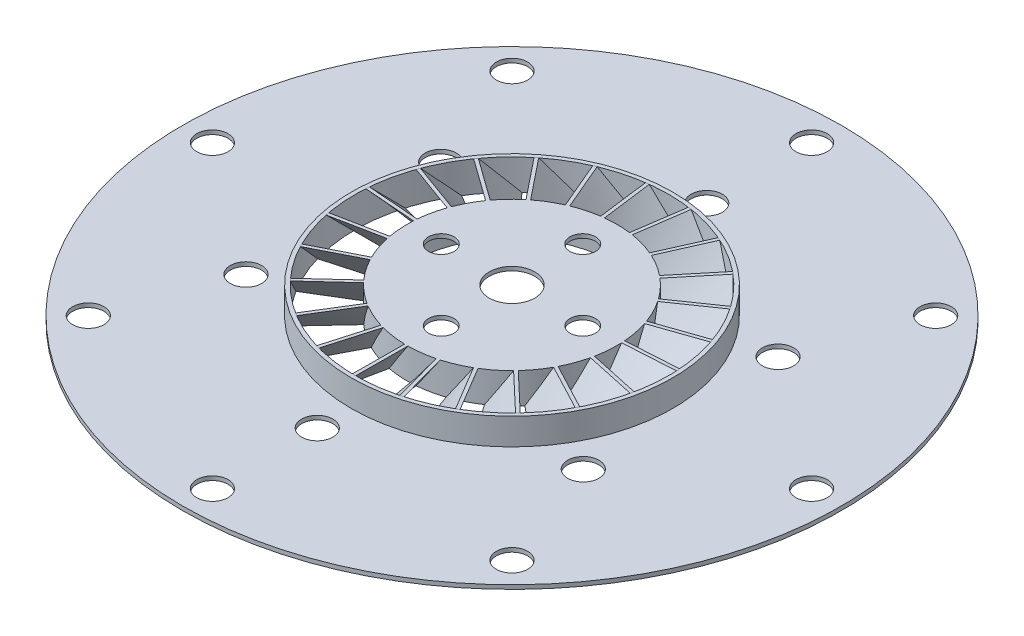
SolidWorks part; units mm, degrees
ref_plane "Front Plane" through (0, 0, 0) normal (0, 0, 1) x (1, 0, 0)
ref_plane "Top Plane" through (0, 0, 0) normal (0, 1, 0) x (1, 0, 0)
ref_plane "Right Plane" through (0, 0, 0) normal (1, 0, 0) x (0, 0, -1)
sketch "Sketch1" plane through (0, 0, 0) normal (0, 1, 0) x (1, 0, 0)
  circle A0 centre (0, 0) radius 33.25
  circle A1 centre (0, 0) radius 34.0882
  circle A2 centre (0, 0) radius 69.85
  circle A3 centre (0, 0) radius 22.25
  circle A4 centre (0, 0) radius 21.4118
  dimension "D1" = 66.5
  dimension "D2" = 0.8382
  dimension "D3" = 139.7
  dimension "D4" = 44.5
  dimension "D5" = 0.8382
extrude "Boss-Extrude1" add sketch "Sketch1" along normal blind 6.5 contours A1 A0 region at (-33.9918, 0, 0)
extrude "Boss-Extrude2" add sketch "Sketch1<3>" along normal blind 0.8636 contours A2 A1 region at (-67.8743, 0, 0)
sketch "Sketch1<3>" plane through (0, 0, 0) normal (0, 1, 0) x (1, 0, 0) same geometry as "Sketch1"
extrude "Boss-Extrude3" add sketch "Sketch1<4>" along normal blind 6.5 separate body contours A3 A4 region at (-21.6207, 0, 0)
sketch "Sketch1<4>" plane through (0, 0, 0) normal (0, 1, 0) x (1, 0, 0) same geometry as "Sketch1"
extrude "Boss-Extrude4" add sketch "Sketch1<5>" along normal blind 0.7 contours A4 region at (0, 0, 0)
sketch "Sketch1<5>" plane through (0, 0, 0) normal (0, 1, 0) x (1, 0, 0) same geometry as "Sketch1"
sketch "Sketch2" plane through (0, 0, 0) normal (0, -1, 0) x (1, 0, 0)
  line L0 (-31.9208, 9.3073) -> (-21.3278, 6.3393)
  line L1 (-33.2482, 0.35) -> (-22.2472, 0.35)
  line L2 (-33.2482, -0.35) -> (-22.2472, -0.35)
  line L3 (-32.1097, 8.6332) -> (-21.5167, 5.6652)
  line L4 (-28.226, 17.5743) -> (-18.8266, 11.8584)
  line L5 (-28.5897, 16.9762) -> (-19.1903, 11.2603)
  line L6 (-22.4378, 24.5378) -> (-14.9291, 16.498)
  line L7 (-22.9494, 24.0601) -> (-15.4407, 16.0202)
  line L8 (-14.9856, 29.6816) -> (-9.9244, 19.914)
  line L9 (-15.6071, 29.3595) -> (-10.5459, 19.592)
  line L10 (-6.4219, 32.624) -> (-4.1837, 21.8531)
  line L11 (-7.1072, 32.4815) -> (-4.869, 21.7107)
  line L12 (2.6181, 33.1468) -> (1.8674, 22.1715)
  line L13 (1.9198, 33.1945) -> (1.169, 22.2193)
  line L14 (11.4639, 31.2112) -> (7.7799, 20.8455)
  line L15 (10.8043, 31.4456) -> (7.1204, 21.0799)
  line L16 (19.4595, 26.9609) -> (13.1155, 17.9735)
  line L17 (18.8876, 27.3646) -> (12.5436, 18.3772)
  line L18 (26.0119, 20.711) -> (17.4783, 13.7685)
  line L19 (25.5701, 21.254) -> (17.0366, 14.3115)
  line L20 (30.635, 12.9251) -> (20.5449, 8.5423)
  line L21 (30.3561, 13.5671) -> (20.266, 9.1844)
  line L22 (32.9861, 4.1806) -> (22.0877, 2.6826)
  line L23 (32.8908, 4.874) -> (21.9924, 3.3761)
  line L24 (32.8908, -4.874) -> (21.9924, -3.3761)
  line L25 (32.9861, -4.1806) -> (22.0877, -2.6826)
  line L26 (30.3561, -13.5671) -> (20.266, -9.1844)
  line L27 (30.635, -12.9251) -> (20.5449, -8.5423)
  line L28 (25.5701, -21.254) -> (17.0366, -14.3115)
  line L29 (26.0119, -20.711) -> (17.4783, -13.7685)
  line L30 (18.8876, -27.3646) -> (12.5436, -18.3772)
  line L31 (19.4595, -26.9609) -> (13.1155, -17.9735)
  line L32 (10.8043, -31.4456) -> (7.1204, -21.0799)
  line L33 (11.4639, -31.2112) -> (7.7799, -20.8455)
  line L34 (1.9198, -33.1945) -> (1.169, -22.2193)
  line L35 (2.6181, -33.1468) -> (1.8674, -22.1715)
  line L36 (-7.1072, -32.4815) -> (-4.869, -21.7107)
  line L37 (-6.4219, -32.624) -> (-4.1837, -21.8531)
  line L38 (-15.6071, -29.3595) -> (-10.5459, -19.592)
  line L39 (-14.9856, -29.6816) -> (-9.9244, -19.914)
  line L40 (-22.9494, -24.0601) -> (-15.4407, -16.0202)
  line L41 (-22.4378, -24.5378) -> (-14.9291, -16.498)
  line L42 (-28.5897, -16.9762) -> (-19.1903, -11.2603)
  line L43 (-28.226, -17.5743) -> (-18.8266, -11.8584)
  line L44 (-32.1097, -8.6332) -> (-21.5167, -5.6652)
  line L45 (-31.9208, -9.3073) -> (-21.3278, -6.3393)
  circle A0 centre (0, 0) radius 33.25 construction
  circle A1 centre (0, 0) radius 22.25
  arc A2 (-21.3278, 6.3393) -> (-21.5167, 5.6652) centre (0, 0) ccw
  arc A3 (-18.8266, 11.8584) -> (-19.1903, 11.2603) centre (0, 0) ccw
  circle A5 centre (0, 0) radius 22.25 construction
  arc A6 (-31.9208, 9.3073) -> (-32.1097, 8.6332) centre (0, 0) ccw
  arc A7 (-28.226, 17.5743) -> (-28.5897, 16.9762) centre (0, 0) ccw
  arc A8 (-22.4378, 24.5378) -> (-22.9494, 24.0601) centre (0, 0) ccw
  arc A9 (-14.9291, 16.498) -> (-15.4407, 16.0202) centre (0, 0) ccw
  arc A10 (-9.9244, 19.914) -> (-10.5459, 19.592) centre (0, 0) ccw
  arc A11 (-14.9856, 29.6816) -> (-15.6071, 29.3595) centre (0, 0) ccw
  arc A12 (-6.4219, 32.624) -> (-7.1072, 32.4815) centre (0, 0) ccw
  arc A13 (-4.1837, 21.8531) -> (-4.869, 21.7107) centre (0, 0) ccw
  arc A14 (1.8674, 22.1715) -> (1.169, 22.2193) centre (0, 0) ccw
  arc A15 (2.6181, 33.1468) -> (1.9198, 33.1945) centre (0, 0) ccw
  arc A16 (11.4639, 31.2112) -> (10.8043, 31.4456) centre (0, 0) ccw
  arc A17 (7.7799, 20.8455) -> (7.1204, 21.0799) centre (0, 0) ccw
  arc A18 (13.1155, 17.9735) -> (12.5436, 18.3772) centre (0, 0) ccw
  arc A19 (19.4595, 26.9609) -> (18.8876, 27.3646) centre (0, 0) ccw
  arc A20 (26.0119, 20.711) -> (25.5701, 21.254) centre (0, 0) ccw
  arc A21 (17.4783, 13.7685) -> (17.0366, 14.3115) centre (0, 0) ccw
  arc A22 (20.5449, 8.5423) -> (20.266, 9.1844) centre (0, 0) ccw
  arc A23 (30.635, 12.9251) -> (30.3561, 13.5671) centre (0, 0) ccw
  arc A24 (32.9861, 4.1806) -> (32.8908, 4.874) centre (0, 0) ccw
  arc A25 (22.0877, 2.6826) -> (21.9924, 3.3761) centre (0, 0) ccw
  arc A26 (21.9924, -3.3761) -> (22.0877, -2.6826) centre (0, 0) ccw
  arc A27 (32.8908, -4.874) -> (32.9861, -4.1806) centre (0, 0) ccw
  arc A28 (-22.2472, 0.35) -> (-22.2472, -0.35) centre (0, 0) ccw
  arc A29 (-33.2482, 0.35) -> (-33.2482, -0.35) centre (0, 0) ccw
  arc A30 (-21.5167, -5.6652) -> (-21.3278, -6.3393) centre (0, 0) ccw
  arc A31 (-32.1097, -8.6332) -> (-31.9208, -9.3073) centre (0, 0) ccw
  arc A32 (-19.1903, -11.2603) -> (-18.8266, -11.8584) centre (0, 0) ccw
  arc A33 (-28.5897, -16.9762) -> (-28.226, -17.5743) centre (0, 0) ccw
  arc A34 (-22.9494, -24.0601) -> (-22.4378, -24.5378) centre (0, 0) ccw
  arc A35 (-15.4407, -16.0202) -> (-14.9291, -16.498) centre (0, 0) ccw
  arc A36 (-10.5459, -19.592) -> (-9.9244, -19.914) centre (0, 0) ccw
  arc A37 (-15.6071, -29.3595) -> (-14.9856, -29.6816) centre (0, 0) ccw
  arc A38 (-7.1072, -32.4815) -> (-6.4219, -32.624) centre (0, 0) ccw
  arc A39 (-4.869, -21.7107) -> (-4.1837, -21.8531) centre (0, 0) ccw
  arc A40 (1.169, -22.2193) -> (1.8674, -22.1715) centre (0, 0) ccw
  arc A41 (1.9198, -33.1945) -> (2.6181, -33.1468) centre (0, 0) ccw
  arc A42 (10.8043, -31.4456) -> (11.4639, -31.2112) centre (0, 0) ccw
  arc A43 (7.1204, -21.0799) -> (7.7799, -20.8455) centre (0, 0) ccw
  arc A44 (12.5436, -18.3772) -> (13.1155, -17.9735) centre (0, 0) ccw
  arc A45 (18.8876, -27.3646) -> (19.4595, -26.9609) centre (0, 0) ccw
  arc A46 (25.5701, -21.254) -> (26.0119, -20.711) centre (0, 0) ccw
  arc A47 (17.0366, -14.3115) -> (17.4783, -13.7685) centre (0, 0) ccw
  arc A48 (20.266, -9.1844) -> (20.5449, -8.5423) centre (0, 0) ccw
  arc A49 (30.3561, -13.5671) -> (30.635, -12.9251) centre (0, 0) ccw
  point P106 (0, 0)
  dimension "D3" = 0.7
  dimension "D1" = 0
  dimension "D4" = 23
sketch "Sketch3" plane through (0, 6.5, 0) normal (0, 1, 0) x (1, 0, 0)
  line L0 (0, 0) -> (-32.6054, -6.5152) construction
  line L1 (0, 0) -> (-15.6581, 0) construction
  line L2 (-21.8846, -4.016) -> (-32.6722, -6.1716)
  line L3 (-21.7474, -4.7025) -> (-32.535, -6.8581)
  line L4 (-22.1565, 2.0373) -> (-33.1257, 2.8721)
  line L5 (-22.2097, 1.3393) -> (-33.1788, 2.1741)
  line L6 (-20.7853, 7.9395) -> (-31.1225, 11.7028)
  line L7 (-21.0247, 7.2817) -> (-31.3619, 11.045)
  line L8 (-17.8724, 13.2529) -> (-26.811, 19.6656)
  line L9 (-18.2805, 12.6841) -> (-27.219, 19.0968)
  line L10 (-13.6341, 17.5833) -> (-20.511, 26.1698)
  line L11 (-14.1805, 17.1457) -> (-21.0574, 25.7322)
  line L12 (-8.3846, 20.6097) -> (-12.6899, 30.7332)
  line L13 (-9.0288, 20.3358) -> (-13.3341, 30.4592)
  line L14 (-2.5132, 22.1076) -> (-3.9276, 33.0172)
  line L15 (-3.2074, 22.0176) -> (-4.6218, 32.9272)
  line L16 (3.5445, 21.9659) -> (5.126, 32.8525)
  line L17 (2.8518, 22.0665) -> (4.4332, 32.9531)
  line L18 (9.3394, 20.195) -> (13.7994, 30.2513)
  line L19 (8.6995, 20.4788) -> (13.1595, 30.5351)
  line L20 (14.4416, 16.9264) -> (21.4494, 25.4064)
  line L21 (13.902, 17.3723) -> (20.9098, 25.8524)
  line L22 (18.4728, 12.4024) -> (27.5085, 18.6773)
  line L23 (18.0735, 12.9774) -> (27.1093, 19.2523)
  line L24 (21.1339, 6.9586) -> (31.5275, 10.563)
  line L25 (20.9045, 7.6199) -> (31.2982, 11.2244)
  line L26 (22.2276, 0.9987) -> (33.2083, 1.6653)
  line L27 (22.1852, 1.6974) -> (33.1659, 2.364)
  line L28 (21.6728, -5.0353) -> (32.4261, -7.356)
  line L29 (21.8204, -4.351) -> (32.5738, -6.6717)
  line L30 (19.5106, -10.6958) -> (29.239, -15.8316)
  line L31 (19.8374, -10.0768) -> (29.5658, -15.2126)
  line L32 (15.9014, -15.563) -> (23.8835, -23.1332)
  line L33 (16.3831, -15.0551) -> (24.3652, -22.6252)
  line L34 (11.1129, -19.2761) -> (16.7565, -28.719)
  line L35 (11.7137, -18.917) -> (17.3574, -28.3599)
  line L36 (5.5001, -21.5595) -> (8.3869, -32.1749)
  line L37 (6.1756, -21.3758) -> (9.0623, -31.9912)
  line L38 (-0.5205, -22.2439) -> (-0.6048, -33.2445)
  line L39 (0.1795, -22.2493) -> (0.0952, -33.2499)
  line L40 (-6.5025, -21.2786) -> (-9.5516, -31.8485)
  line L41 (-5.83, -21.4726) -> (-8.8791, -32.0425)
  line L42 (-12.0023, -18.7352) -> (-17.7901, -28.0905)
  line L43 (-11.407, -19.1035) -> (-17.1948, -28.4588)
  line L44 (-16.6119, -14.8023) -> (-24.7091, -22.2491)
  line L45 (-16.1381, -15.3175) -> (-24.2352, -22.7644)
  line L46 (-19.9895, -9.7715) -> (-29.7956, -14.7576)
  line L47 (-19.6722, -10.3955) -> (-29.4783, -15.3816)
  circle A0 centre (0, 0) radius 33.25 construction
  circle A1 centre (0, 0) radius 22.25 construction
  arc A2 (-32.6722, -6.1716) -> (-32.535, -6.8581) centre (0, 0) ccw
  arc A3 (-21.8846, -4.016) -> (-21.7474, -4.7025) centre (0, 0) ccw
  arc A4 (-22.1565, 2.0373) -> (-22.2097, 1.3393) centre (0, 0) ccw
  arc A5 (-33.1257, 2.8721) -> (-33.1788, 2.1741) centre (0, 0) ccw
  arc A6 (-20.7853, 7.9395) -> (-21.0247, 7.2817) centre (0, 0) ccw
  arc A7 (-31.1225, 11.7028) -> (-31.3619, 11.045) centre (0, 0) ccw
  arc A8 (-17.8724, 13.2529) -> (-18.2805, 12.6841) centre (0, 0) ccw
  arc A9 (-26.811, 19.6656) -> (-27.219, 19.0968) centre (0, 0) ccw
  arc A10 (-13.6341, 17.5833) -> (-14.1805, 17.1457) centre (0, 0) ccw
  arc A11 (-20.511, 26.1698) -> (-21.0574, 25.7322) centre (0, 0) ccw
  arc A12 (-8.3846, 20.6097) -> (-9.0288, 20.3358) centre (0, 0) ccw
  arc A13 (-12.6899, 30.7332) -> (-13.3341, 30.4592) centre (0, 0) ccw
  arc A14 (-2.5132, 22.1076) -> (-3.2074, 22.0176) centre (0, 0) ccw
  arc A15 (-3.9276, 33.0172) -> (-4.6218, 32.9272) centre (0, 0) ccw
  arc A16 (3.5445, 21.9659) -> (2.8518, 22.0665) centre (0, 0) ccw
  arc A17 (5.126, 32.8525) -> (4.4332, 32.9531) centre (0, 0) ccw
  arc A18 (9.3394, 20.195) -> (8.6995, 20.4788) centre (0, 0) ccw
  arc A19 (13.7994, 30.2513) -> (13.1595, 30.5351) centre (0, 0) ccw
  arc A20 (14.4416, 16.9264) -> (13.902, 17.3723) centre (0, 0) ccw
  arc A21 (21.4494, 25.4064) -> (20.9098, 25.8524) centre (0, 0) ccw
  arc A22 (18.4728, 12.4024) -> (18.0735, 12.9774) centre (0, 0) ccw
  arc A23 (27.5085, 18.6773) -> (27.1093, 19.2523) centre (0, 0) ccw
  arc A24 (21.1339, 6.9586) -> (20.9045, 7.6199) centre (0, 0) ccw
  arc A25 (31.5275, 10.563) -> (31.2982, 11.2244) centre (0, 0) ccw
  arc A26 (22.2276, 0.9987) -> (22.1852, 1.6974) centre (0, 0) ccw
  arc A27 (33.2083, 1.6653) -> (33.1659, 2.364) centre (0, 0) ccw
  arc A28 (21.6728, -5.0353) -> (21.8204, -4.351) centre (0, 0) ccw
  arc A29 (32.4261, -7.356) -> (32.5738, -6.6717) centre (0, 0) ccw
  arc A30 (19.5106, -10.6958) -> (19.8374, -10.0768) centre (0, 0) ccw
  arc A31 (29.239, -15.8316) -> (29.5658, -15.2126) centre (0, 0) ccw
  arc A32 (15.9014, -15.563) -> (16.3831, -15.0551) centre (0, 0) ccw
  arc A33 (23.8835, -23.1332) -> (24.3652, -22.6252) centre (0, 0) ccw
  arc A34 (11.1129, -19.2761) -> (11.7137, -18.917) centre (0, 0) ccw
  arc A35 (16.7565, -28.719) -> (17.3574, -28.3599) centre (0, 0) ccw
  arc A36 (5.5001, -21.5595) -> (6.1756, -21.3758) centre (0, 0) ccw
  arc A37 (8.3869, -32.1749) -> (9.0623, -31.9912) centre (0, 0) ccw
  arc A38 (-0.5205, -22.2439) -> (0.1795, -22.2493) centre (0, 0) ccw
  arc A39 (-0.6048, -33.2445) -> (0.0952, -33.2499) centre (0, 0) ccw
  arc A40 (-6.5025, -21.2786) -> (-5.83, -21.4726) centre (0, 0) ccw
  arc A41 (-9.5516, -31.8485) -> (-8.8791, -32.0425) centre (0, 0) ccw
  arc A42 (-12.0023, -18.7352) -> (-11.407, -19.1035) centre (0, 0) ccw
  arc A43 (-17.7901, -28.0905) -> (-17.1948, -28.4588) centre (0, 0) ccw
  arc A44 (-16.6119, -14.8023) -> (-16.1381, -15.3175) centre (0, 0) ccw
  arc A45 (-24.7091, -22.2491) -> (-24.2352, -22.7644) centre (0, 0) ccw
  arc A46 (-19.9895, -9.7715) -> (-19.6722, -10.3955) centre (0, 0) ccw
  arc A47 (-29.7956, -14.7576) -> (-29.4783, -15.3816) centre (0, 0) ccw
  point P101 (0, 0)
  dimension "D1" = 11.3
  dimension "D2" = 0.35
  dimension "D3" = 0.35
  dimension "D4" = 23
loft "Loft1" add section "Sketch2" section "Sketch3" connector at (-32.1097, 0, 8.6332) connector at (-29.7956, 6.5, 14.7576)
pattern_circular "CirPattern1" count 23 over 360 about axis through (0, 6.5, 0) along (0, -1, 0) of "Loft1"
sketch "Sketch4" plane through (0, 6.5, 0) normal (0, 1, 0) x (1, 0, 0)
  circle A0 centre (0, 0) radius 21.55
  dimension "D1" = 43.1
extrude "Boss-Extrude5" add sketch "Sketch4" against normal blind 0.8382
sketch "Sketch6" plane through (0, 0, 0) normal (0, -1, 0) x (1, 0, 0)
  line L0 (0, 0) -> (0, 14.9949) construction
  line L1 (0, 0) -> (14.9949, 0) construction
  line L2 (0, 0) -> (0, -14.9949) construction
  line L3 (0, 0) -> (-14.9949, 0) construction
  point P9 (0, 0)
  dimension "D1" = 14.9949
  dimension "D2" = 4
hole_wizard "CBORE for M5 Hex Head Bolt1" positions "3DSketch4" profile "Sketch7" counterbore size "M5" standard "ANSI Metric" end condition through all
sketch3d "3DSketch4"
  point P0 (0, 0, 14.9949)
  point P3 (14.9949, 0, 0)
  point P6 (0, 0, -14.9949)
  point P9 (-14.9949, 0, 0)
sketch "Sketch7" plane through (0, 0, 14.9949) normal (1, 0, 0) x (0, 0, -1)
  line L0 (0, 0) -> (0, 6.5001)
  line L1 (0, 6.5001) -> (2.7, 6.5001)
  line L3 (2.7, 6.5001) -> (2.7, 3.58)
  line L4 (2.7, 3.58) -> (6.12, 3.58)
  line L5 (6.12, 3.58) -> (6.12, 0)
  line L7 (6.12, 0) -> (0, 0)
  line L11 (0, -6.35) -> (0, 107.95) construction
  dimension "Thru Hole Dia." = 5.4
  dimension "Thru Hole Depth" = 6.5001
  dimension "C'Bore Dia." = 12.24
  dimension "C'Bore Depth" = 3.58
sketch "Sketch8" plane through (0, 0, 0) normal (0, -1, 0) x (1, 0, 0)
  circle A0 centre (0, 0) radius 21.39
  arc A1 (22.0877, -2.6826) -> (22.0877, 2.6826) centre (0, 0) ccw construction
  circle A2 centre (0, 0) radius 22.25
  dimension "D1" = 0.86
  dimension "D2" = 44.5
extrude "Cut-Extrude1" cut sketch "Sketch8" against normal blind 1.5 contours A0 region at (0, 0, 0)
extrude "Boss-Extrude6" add sketch "Sketch8<2>" against normal up to surface (6.5 mm away) up to face at (0, 6.5, 17.6949)
sketch "Sketch8<2>" plane through (0, 0, 0) normal (0, -1, 0) x (1, 0, 0) same geometry as "Sketch8"
sketch "Sketch9" plane through (0, 5.6618, 0) normal (0, -1, 0) x (1, 0, 0)
  circle A0 centre (0, 0) radius 4.826
  dimension "D1" = 9.652
extrude "Cut-Extrude3" cut sketch "Sketch9" against normal blind 2.54
sketch "Sketch10" plane through (0, 0, 0) normal (0, -1, 0) x (1, 0, 0)
  line L0 (0, 0) -> (0, 63.5) construction
  circle A0 centre (0, 63.5) radius 3.3147
  dimension "D2" = 6.6294
  dimension "D1" = 63.5
extrude "Cut-Extrude4" cut sketch "Sketch10" against normal blind 10
pattern_circular "CirPattern2" count 8 over 360 about axis through (0, 1.5, 0) along (0, -1, 0) of "Cut-Extrude4"
sketch "Sketch11" plane through (0, 0, 0) normal (0, -1, 0) x (1, 0, 0)
  line L0 (0, 0) -> (0, 41.275) construction
  circle A0 centre (0, 41.275) radius 3.3147
  dimension "D2" = 6.6294
  dimension "D1" = 41.275
extrude "Cut-Extrude5" cut sketch "Sketch11" against normal blind 10
pattern_circular "CirPattern3" count 6 over 360 about axis through (0, 1.5, 0) along (0, -1, 0) of "Cut-Extrude5"
